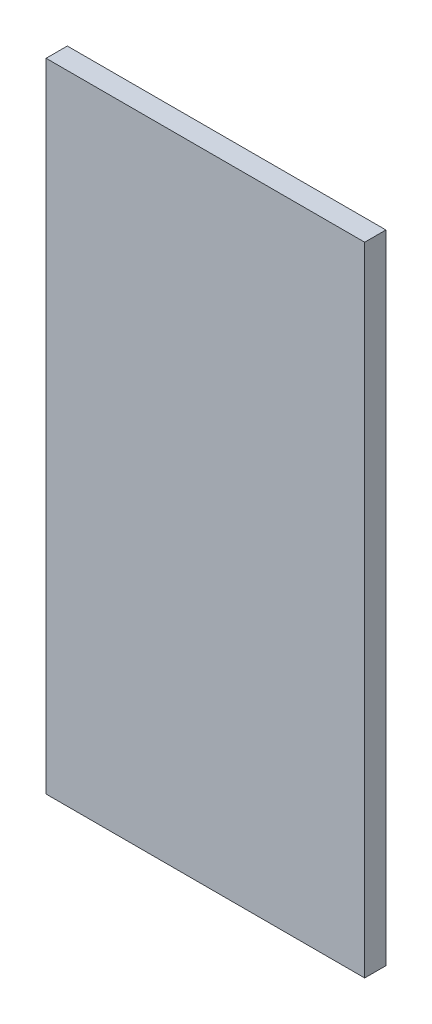
SolidWorks part; units mm, degrees
ref_plane "Alzado" through (0, 0, 0) normal (0, 0, 1) x (1, 0, 0)
ref_plane "Planta" through (0, 0, 0) normal (0, 1, 0) x (1, 0, 0)
ref_plane "Vista lateral" through (0, 0, 0) normal (1, 0, 0) x (0, 0, -1)
ref_plane "Plano1" through (0, 0, 360) normal (0, 0, -1) x (-1, 0, 0)
sketch "Croquis1" plane through (0, 0, 360) normal (0, 0, -1) x (-1, 0, 0)
  line L0 (7.7541, -147.1656) -> (7.7541, -132.1656) construction
  line L1 (-149.7459, -147.1656) -> (165.2541, -147.1656) construction
  line L2 (-149.7459, 182.8344) -> (165.2541, 182.8344) construction
  line L3 (7.7541, 167.8344) -> (7.7541, 182.8344) construction
  line L4 (-67.2459, 167.8344) -> (82.7541, 167.8344)
  line L5 (-67.2459, 167.8344) -> (-67.2459, -132.1656)
  line L6 (-67.2459, -132.1656) -> (82.7541, -132.1656)
  line L7 (82.7541, 167.8344) -> (82.7541, -132.1656)
  point P6 (7.7541, 12.1668)
  dimension "D1" = 150
  dimension "D2" = 300
extrude "Saliente-Extruir1" add sketch "Croquis1" along normal blind 10
